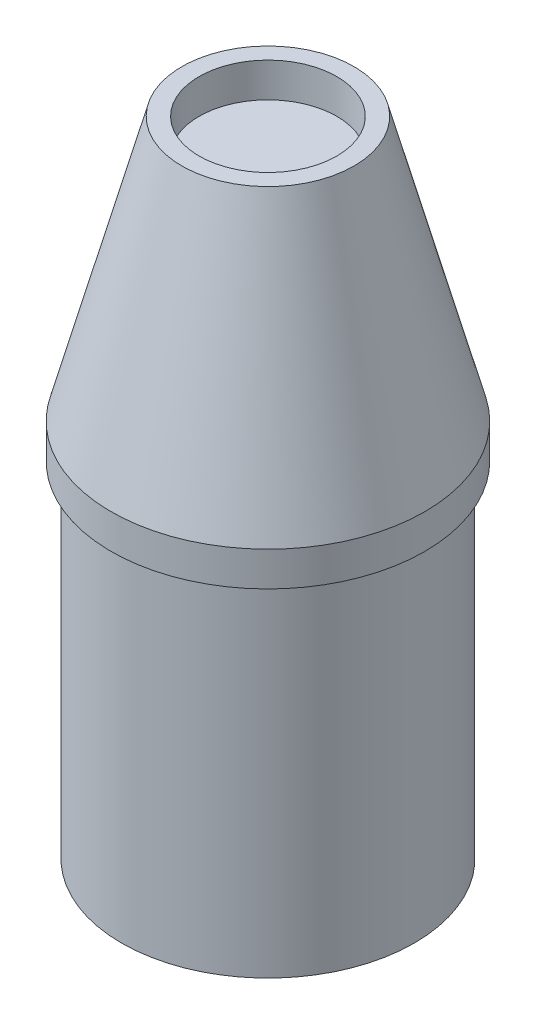
SolidWorks part; units mm, degrees
material "6061 Alloy"
ref_plane "Front Plane" through (0, 0, 0) normal (0, 0, 1) x (1, 0, 0)
ref_plane "Top Plane" through (0, 0, 0) normal (0, 1, 0) x (1, 0, 0)
ref_plane "Right Plane" through (0, 0, 0) normal (1, 0, 0) x (0, 0, -1)
sketch "Sketch1" plane through (0, 0, 0) normal (0, 0, 1) x (1, 0, 0)
  line L0 (0, -26.4747) -> (0, 85.702)
  line L1 (0, 85.702) -> (12.7, 85.702)
  line L2 (12.7, 85.702) -> (12.7, 92.052)
  line L3 (12.7, 92.052) -> (15.875, 92.052)
  line L4 (15.875, 92.052) -> (28.9179, 43.3753)
  line L5 (28.9179, 43.3753) -> (28.9179, 37.0253)
  line L6 (28.9179, 37.0253) -> (26.9875, 37.0253)
  line L7 (26.9875, 37.0253) -> (26.9875, -26.4747)
  line L8 (26.9875, -26.4747) -> (0, -26.4747)
  dimension "D1" = 28.9179
  dimension "D2" = 15
  dimension "D3" = 15.875
  dimension "D5" = 63.5
  dimension "D6" = 6.35
  dimension "D7" = 12.7
  dimension "D8" = 26.9875
revolve "Revolve1" add sketch "Sketch1" angle 360 about L0
